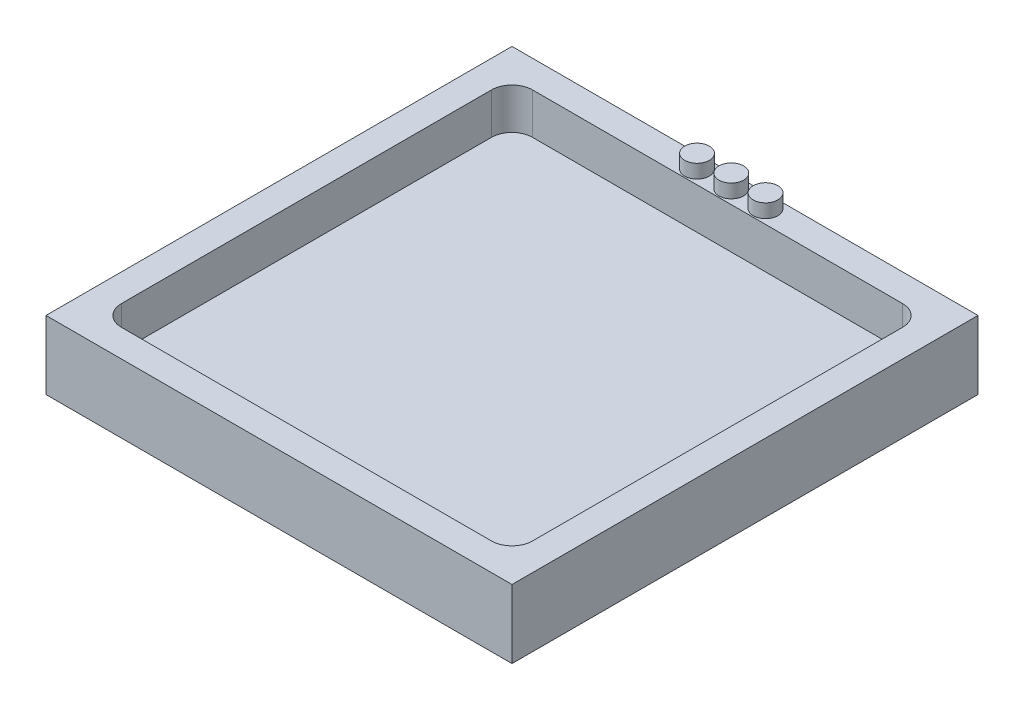
SolidWorks part; units mm, degrees
ref_plane "Front Plane" through (0, 0, 0) normal (0, 0, 1) x (1, 0, 0)
ref_plane "Top Plane" through (0, 0, 0) normal (0, 1, 0) x (1, 0, 0)
ref_plane "Right Plane" through (0, 0, 0) normal (1, 0, 0) x (0, 0, -1)
sketch "Sketch1" plane through (0, 0, 0) normal (0, 1, 0) x (1, 0, 0)
  line L1 (-15, -15) -> (15, -15)
  line L2 (-15, -15) -> (-15, 15)
  line L3 (-15, 15) -> (15, 15)
  line L4 (15, -15) -> (15, 15)
  line L5 (-15, -15) -> (15, 15) construction
  line L6 (-15, 15) -> (15, -15) construction
  line L7 (-17, -17) -> (17, -17)
  line L8 (-17, -17) -> (-17, 17)
  line L9 (-17, 17) -> (17, 17)
  line L10 (17, -17) -> (17, 17)
  line L11 (-17, -17) -> (17, 17) construction
  line L12 (-17, 17) -> (17, -17) construction
  point P0 (0, 0)
  point P6 (0, 0)
  dimension "D1" = 30
  dimension "D2" = 30
  dimension "D3" = 34
  dimension "D4" = 34
extrude "Boss-Extrude2" add sketch "Sketch1" along normal blind 2 contours L3 L4 L1 L2
extrude "Boss-Extrude3" add sketch "Sketch1<6>" along normal blind 5
sketch "Sketch1<6>" plane through (0, 0, 0) normal (0, 1, 0) x (1, 0, 0) same geometry as "Sketch1"
fillet "Fillet1" radius 1.5 4 edges at (15, 3.5, -15) (-15, 3.5, -15) (-15, 3.5, 15) (15, 3.5, 15)
sketch "Sketch2" plane through (0, 5, 0) normal (0, 1, 0) x (1, 0, 0)
  line L2 (0, -1.1) -> (0, 1.1) construction
  line L3 (-17, 17) -> (17, 17) construction
  circle A0 centre (0, 16) radius 0.9
  circle A1 centre (2.5, 16) radius 0.9
  circle A2 centre (-2.5, 16) radius 0.9
  dimension "D1" = 1
  dimension "D2" = 1.8
  dimension "D3" = 1.8
  dimension "D5" = 2.5
  dimension "D4" = 2.5
extrude "Boss-Extrude4" add sketch "Sketch2" along normal blind 1
